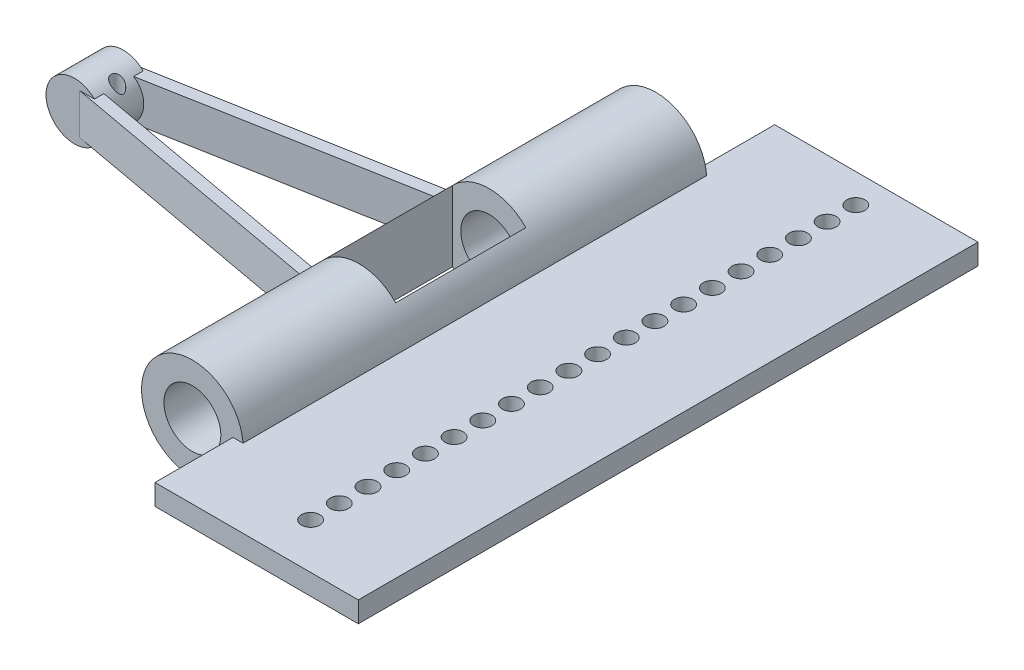
SolidWorks part; units mm, degrees
material "Gray Cast Iron"
ref_plane "Front Plane" through (0, 0, 0) normal (0, 0, 1) x (1, 0, 0)
ref_plane "Top Plane" through (0, 0, 0) normal (0, 1, 0) x (1, 0, 0)
ref_plane "Right Plane" through (0, 0, 0) normal (1, 0, 0) x (0, 0, -1)
sketch "Sketch1" plane through (0, 0, 0) normal (0, 0, 1) x (1, 0, 0)
  circle A0 centre (0, 7) radius 12.5
  dimension "D2" = 25
  dimension "D1" = 7
extrude "Boss-Extrude1" add sketch "Sketch1" along normal mid plane 114
sketch "Sketch2" plane through (0, 0, 0) normal (0, 0, 1) x (1, 0, 0)
  circle A0 centre (0, 7) radius 7
  dimension "D2" = 14
  dimension "D1" = 7
extrude "Cut-Extrude1" cut sketch "Sketch2" against normal mid plane 120
sketch "Sketch3" plane through (0, 0, 0) normal (0, 1, 0) x (1, 0, 0)
  line L0 (-9, -16) -> (9, -16)
  line L1 (9, -16) -> (9, 16)
  line L2 (9, 16) -> (-9, 16)
  line L3 (-9, 16) -> (-9, -16)
  dimension "D1" = 18
  dimension "D2" = 32
  dimension "D3" = 9
  dimension "D4" = 16
extrude "Cut-Extrude2" cut sketch "Sketch3" against normal mid plane 60
sketch "Sketch4" plane through (0, 0, 0) normal (0, 1, 0) x (1, 0, 0)
  line L0 (10, -76.2) -> (60, -76.2)
  line L1 (60, -76.2) -> (60, 76.2)
  line L2 (60, 76.2) -> (10, 76.2)
  line L3 (10, 76.2) -> (10, -76.2)
  circle A0 centre (37.1, 69.05) radius 2.25
  circle A1 centre (37.1, 61.9935) radius 2.25
  circle A2 centre (37.1, 54.937) radius 2.25
  circle A3 centre (37.1, 47.8805) radius 2.25
  circle A4 centre (37.1, 40.824) radius 2.25
  circle A5 centre (37.1, 33.7675) radius 2.25
  circle A6 centre (37.1, 26.711) radius 2.25
  circle A7 centre (37.1, 19.6545) radius 2.25
  circle A8 centre (37.1, 12.598) radius 2.25
  circle A9 centre (37.1, 5.5415) radius 2.25
  circle A10 centre (37.1, -1.515) radius 2.25
  circle A11 centre (37.1, -8.5715) radius 2.25
  circle A12 centre (37.1, -15.628) radius 2.25
  circle A13 centre (37.1, -22.6845) radius 2.25
  circle A14 centre (37.1, -29.741) radius 2.25
  circle A15 centre (37.1, -36.7975) radius 2.25
  circle A16 centre (37.1, -43.854) radius 2.25
  circle A17 centre (37.1, -50.9105) radius 2.25
  circle A18 centre (37.1, -57.967) radius 2.25
  circle A19 centre (37.1, -65.0235) radius 2.25
  dimension "D3" = 4.5
  dimension "D6" = 4.5
  dimension "D9" = 4.5
  dimension "D12" = 4.5
  dimension "D15" = 4.5
  dimension "D18" = 4.5
  dimension "D21" = 4.5
  dimension "D24" = 4.5
  dimension "D27" = 4.5
  dimension "D30" = 4.5
  dimension "D33" = 4.5
  dimension "D36" = 4.5
  dimension "D39" = 4.5
  dimension "D42" = 4.5
  dimension "D45" = 4.5
  dimension "D48" = 4.5
  dimension "D51" = 4.5
  dimension "D54" = 4.5
  dimension "D57" = 4.5
  dimension "D60" = 4.5
  dimension "D1" = 37.1
  dimension "D2" = 69.05
  dimension "D4" = 37.1
  dimension "D5" = 61.9935
  dimension "D7" = 37.1
  dimension "D8" = 54.937
  dimension "D10" = 37.1
  dimension "D11" = 47.8805
  dimension "D13" = 37.1
  dimension "D14" = 40.824
  dimension "D16" = 37.1
  dimension "D17" = 33.7675
  dimension "D19" = 37.1
  dimension "D20" = 26.711
  dimension "D22" = 37.1
  dimension "D23" = 19.6545
  dimension "D25" = 37.1
  dimension "D26" = 12.598
  dimension "D28" = 37.1
  dimension "D29" = 5.5415
  dimension "D31" = 37.1
  dimension "D32" = 1.515
  dimension "D34" = 37.1
  dimension "D35" = 8.5715
  dimension "D37" = 37.1
  dimension "D38" = 15.628
  dimension "D40" = 37.1
  dimension "D41" = 22.6845
  dimension "D43" = 37.1
  dimension "D44" = 29.741
  dimension "D46" = 37.1
  dimension "D47" = 36.7975
  dimension "D49" = 37.1
  dimension "D50" = 43.854
  dimension "D52" = 37.1
  dimension "D53" = 50.9105
  dimension "D55" = 37.1
  dimension "D56" = 57.967
  dimension "D58" = 37.1
  dimension "D59" = 65.0235
  dimension "D61" = 50
  dimension "D62" = 152.4
  dimension "D63" = 10
  dimension "D64" = 76.2
extrude "Boss-Extrude2" add sketch "Sketch4" along normal blind 5.1 from offset 2.9
sketch "Sketch5" plane through (0, 0, 0) normal (0, 1, 0) x (1, 0, 0)
  line L0 (-9, 15.68) -> (-9, 18.68)
  line L1 (-9, 18.68) -> (-80, 5.77)
  line L2 (-80, 5.77) -> (-80, 2.77)
  line L3 (-80, 2.77) -> (-9, 15.68)
  line L4 (-9, -15.68) -> (-9, -18.68)
  line L5 (-9, -18.68) -> (-80, -5.77)
  line L6 (-80, -5.77) -> (-80, -2.77)
  line L7 (-80, -2.77) -> (-9, -15.68)
  dimension "D1" = 9
  dimension "D2" = 15.68
  dimension "D3" = 3
  dimension "D4" = 71
  dimension "D5" = 12.91
  dimension "D6" = 3
  dimension "D7" = 9
  dimension "D8" = 15.68
  dimension "D9" = 3
  dimension "D10" = 71
  dimension "D11" = 12.91
  dimension "D12" = 3
extrude "Boss-Extrude3" add sketch "Sketch5" along normal blind 10 from offset 2
sketch "Sketch6" plane through (0, 0, 0) normal (0, 0, 1) x (1, 0, 0)
  circle A0 centre (-80, 7) radius 7
  dimension "D3" = 14
  dimension "D1" = 80
  dimension "D2" = 7
extrude "Boss-Extrude4" add sketch "Sketch6" along normal mid plane 12
sketch "Sketch7" plane through (0, 0, 0) normal (0, 1, 0) x (1, 0, 0)
  circle A0 centre (-75.5, 0) radius 1.5
  dimension "D2" = 3
  dimension "D1" = 75.5
extrude "Cut-Extrude3" cut sketch "Sketch7" against normal mid plane 28
ref_axis "Axis1" through (0, 0, -83.82) along (0, 0, 1)
ref_plane "Plane1" through (0, 0, 0) normal (1, 0, 0) x (0, 0, -1)
ref_axis "Axis2" through (0, 0, -83.82) along (0, 0, 1)
